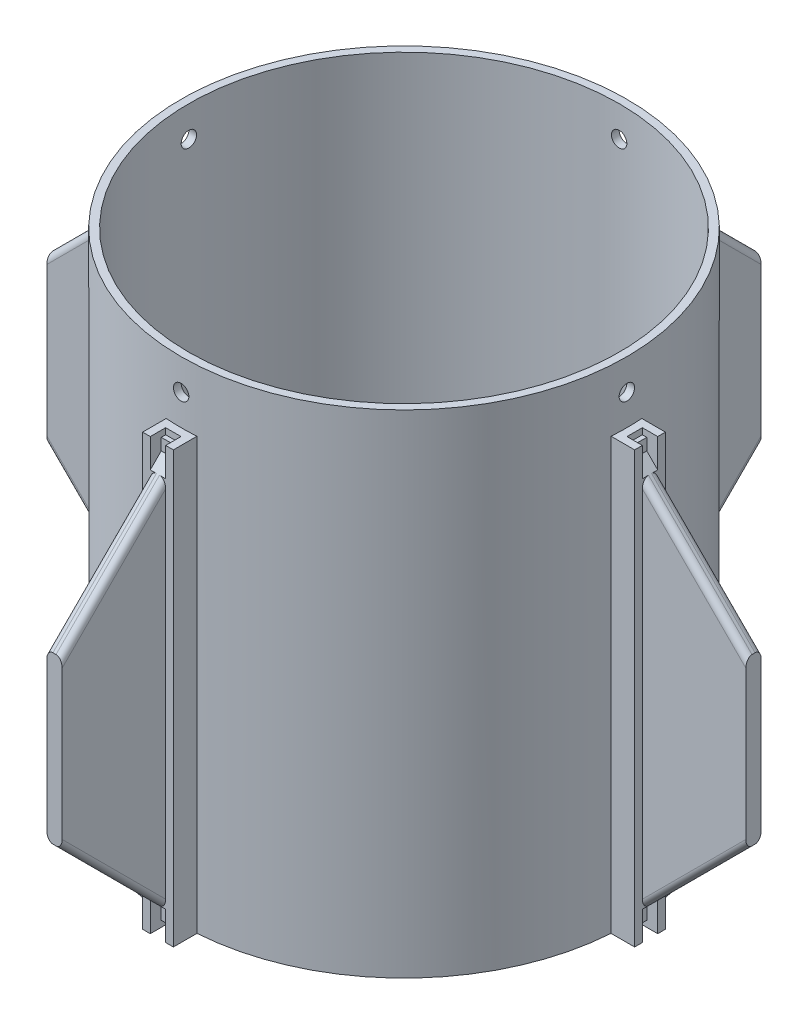
SolidWorks part; units mm, degrees
ref_plane "Front Plane" through (0, 0, 0) normal (0, 0, 1) x (1, 0, 0)
ref_plane "Top Plane" through (0, 0, 0) normal (0, 1, 0) x (1, 0, 0)
ref_plane "Right Plane" through (0, 0, 0) normal (1, 0, 0) x (0, 0, -1)
sketch "Sketch1" plane through (0, 0, 0) normal (0, 1, 0) x (1, 0, 0)
  circle A0 centre (0, 0) radius 92.075
  circle A1 centre (0, 0) radius 88.9
  dimension "D1" = 184.15
  dimension "D2" = 177.8
extrude "Base Shell" add sketch "Sketch1" along normal blind 203.2
sketch "Sketch2" plane through (0, 0, 0) normal (0, -1, 0) x (1, 0, 0)
  circle A1 centre (0, 0) radius 69.85 construction
  circle A2 centre (0, 0) radius 88.9 construction
  circle A3 centre (0, 0) radius 88.9
  arc A4 (-78.8035, -9.5078) -> (-9.5078, -78.8035) centre (0, 0) ccw
  circle A5 centre (0, 79.375) radius 3.175
  circle A6 centre (79.375, 0) radius 3.175
  circle A7 centre (0, -79.375) radius 3.175
  circle A8 centre (-79.375, 0) radius 3.175
  arc A9 (-9.5078, 78.8035) -> (9.5078, 78.8035) centre (0, 79.375) ccw
  arc A10 (78.8035, 9.5078) -> (78.8035, -9.5078) centre (79.375, 0) ccw
  arc A11 (9.5078, -78.8035) -> (-9.5078, -78.8035) centre (0, -79.375) ccw
  arc A12 (-78.8035, -9.5078) -> (-78.8035, 9.5078) centre (-79.375, 0) ccw
  arc A13 (-9.5078, 78.8035) -> (-78.8035, 9.5078) centre (0, 0) ccw
  arc A14 (78.8035, 9.5078) -> (9.5078, 78.8035) centre (0, 0) ccw
  arc A15 (9.5078, -78.8035) -> (78.8035, -9.5078) centre (0, 0) ccw
  point P18 (0, 0)
  point P26 (0, 0)
  dimension "D1" = 139.7
extrude "Bolt Insert" add sketch "Sketch2" against normal blind 6.35
sketch "Sketch3" plane through (0, 0, 0) normal (0, 1, 0) x (1, 0, 0)
  line L0 (-6.35, 0) -> (6.35, 0)
  line L7 (-6.35, 101.6) -> (-3.175, 101.6)
  line L9 (0, 101.6) -> (0, 92.075) construction
  line L10 (-6.35, 101.6) -> (-5.7435, 91.8957) construction
  line L11 (-6.35, 91.8558) -> (-6.35, 101.6)
  line L12 (5.7435, 91.8957) -> (6.35, 101.6) construction
  line L14 (6.35, 91.8558) -> (6.35, 101.6)
  line L15 (-3.175, 101.6) -> (-3.175, 95.25)
  line L16 (-3.175, 95.25) -> (3.175, 95.25)
  line L17 (3.175, 101.6) -> (3.175, 95.25)
  line L18 (0, 101.6) -> (3.175, 95.25) construction
  line L19 (-3.175, 95.25) -> (0, 101.6) construction
  line L20 (3.175, 101.6) -> (6.35, 101.6)
  circle A2 centre (0, 0) radius 92.075 construction
  arc A3 (6.35, 91.8558) -> (-6.35, 91.8558) centre (0, 0) ccw
  point P1 (0, 101.6)
  dimension "D1" = 12.7
  dimension "D2" = 101.6
  dimension "D3" = 6.35
  dimension "D4" = 3.175
  dimension "D5" = 3.175
extrude "Fin Bracket" add sketch "Sketch3" along normal blind 177.8 contours A3 L14 L20 L17 L16 L15 L7 L11 region at (-4.7625, 0, -101.4399)
pattern_circular "CirPattern1" count 4 over 360 about axis through (0, 203.2, 0) along (0, -1, 0) of "Fin Bracket"
sketch "Sketch4" plane through (0, 0, 0) normal (0, 0, 1) x (1, 0, 0)
  line L0 (0, 0) -> (95.25, 0) construction
  line L1 (91.8558, 2.54) -> (91.8558, 175.26)
  line L6 (91.8558, 177.8) -> (91.8558, 0) construction
  line L8 (91.8558, 2.54) -> (91.8558, 175.26)
  line L12 (91.8558, 175.26) -> (97.0711, 175.26)
  line L13 (97.0711, 170.3979) -> (97.0711, 175.26)
  line L14 (144.3397, 123.1293) -> (97.0711, 170.3979)
  line L15 (144.3397, 54.6707) -> (144.3397, 123.1293)
  line L16 (97.0711, 7.4021) -> (144.3397, 54.6707)
  line L17 (97.0711, 2.54) -> (97.0711, 7.4021)
  line L18 (91.8558, 2.54) -> (97.0711, 2.54)
extrude "Base Fin" add sketch "Sketch4" along normal mid plane 6.35 contours L1 region at (114.2323, 88.9, 0)
pattern_circular "Fin Pattern" count 4 over 360 about axis through (0, 203.2, 0) along (0, -1, 0) of "Base Fin"
fillet "Fin Fillets" radius 2.54 16 edges at (122.9699, 33.3009, 3.175) (122.9699, 33.3009, -3.175) (122.9699, 144.4991, -3.175) (122.9699, 144.4991, 3.175) (3.175, 33.3009, -122.9699) (-3.175, 33.3009, -122.9699) (3.175, 144.4991, -122.9699) (-3.175, 144.4991, -122.9699) (-122.9699, 144.4991, 3.175) (-122.9699, 144.4991, -3.175) (-122.9699, 33.3009, -3.175) (-122.9699, 33.3009, 3.175) (3.175, 33.3009, 122.9699) (-3.175, 33.3009, 122.9699) (3.175, 144.4991, 122.9699) (-3.175, 144.4991, 122.9699)
sketch "Sketch5" plane through (0, 0, 0) normal (0, 0, 1) x (1, 0, 0)
  line L0 (0, 203.2) -> (0, 177.8) construction
  line L1 (92.075, 203.2) -> (-92.075, 203.2) construction
  line L2 (6.35, 177.8) -> (-6.35, 177.8) construction
  circle A0 centre (0, 190.5) radius 3.175
  dimension "D1" = 6.35
extrude "Cut-Extrude1" cut sketch "Sketch5" against normal through all both and the other way through all
sketch "Sketch6" plane through (0, 0, 0) normal (1, 0, 0) x (0, 0, -1)
  line L0 (0, 203.2) -> (0, 177.8) construction
  line L1 (88.9, 203.2) -> (-88.9, 203.2) construction
  line L2 (3.175, 177.8) -> (-3.175, 177.8) construction
  circle A0 centre (0, 190.5) radius 3.175
  dimension "D1" = 6.35
extrude "Cut-Extrude2" cut sketch "Sketch6" against normal through all both and the other way through all
